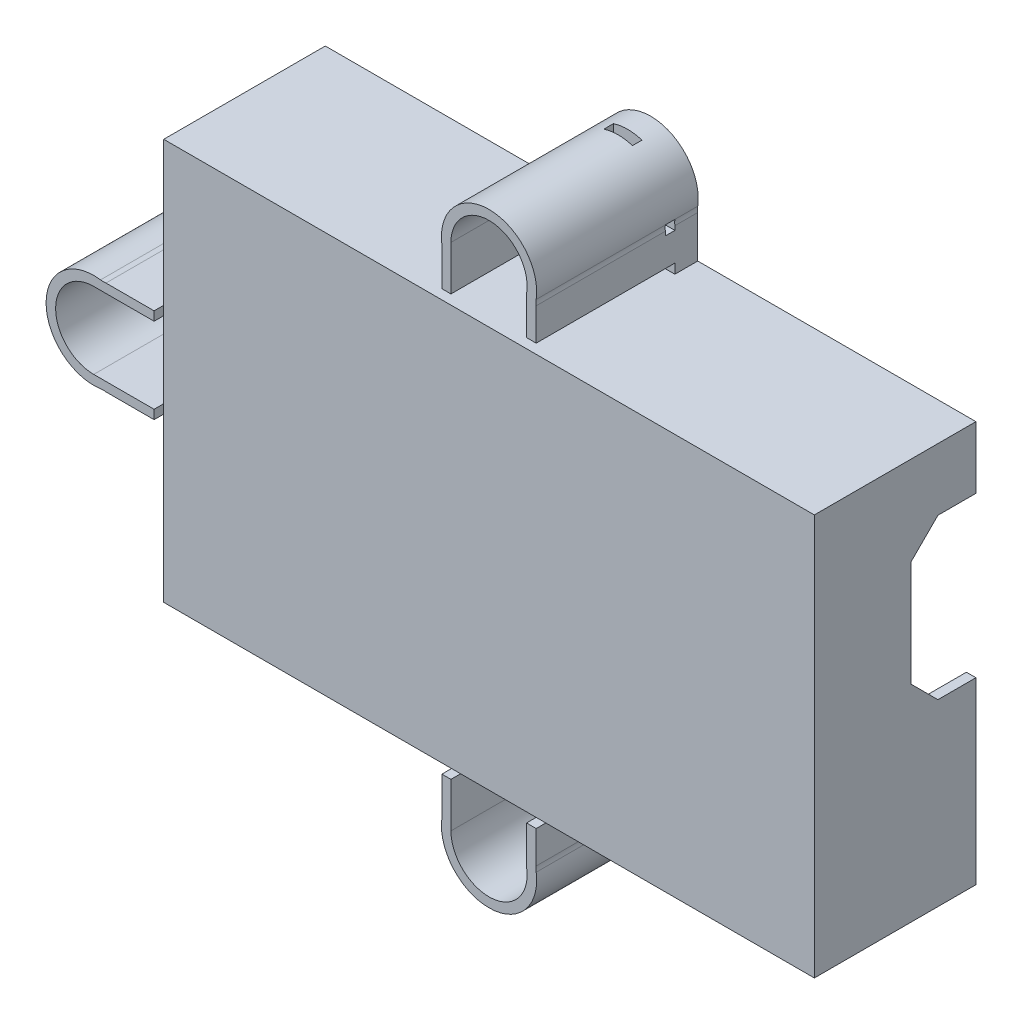
SolidWorks part; units mm, degrees
ref_plane "Front Plane" through (0, 0, 0) normal (0, 0, 1) x (1, 0, 0)
ref_plane "Top Plane" through (0, 0, 0) normal (0, 1, 0) x (1, 0, 0)
ref_plane "Right Plane" through (0, 0, 0) normal (1, 0, 0) x (0, 0, -1)
sketch "Sketch1" plane through (0, 0, 0) normal (0, 0, 1) x (1, 0, 0)
  line L0 (-16.375, 9.825) -> (16.375, -9.825) construction
  line L1 (-16.375, -9.825) -> (-16.575, -9.825) construction
  line L2 (16.575, 10.025) -> (-16.575, 10.025)
  line L3 (16.575, 10.025) -> (16.575, -10.025)
  line L4 (-16.375, 9.825) -> (-16.375, -9.825)
  line L5 (-16.375, -9.825) -> (16.375, -9.825)
  line L6 (16.375, -9.825) -> (16.375, 9.825)
  line L7 (16.375, 9.825) -> (-16.375, 9.825)
  line L8 (-16.375, 9.825) -> (-16.375, -9.825)
  line L9 (-16.375, -9.825) -> (16.375, -9.825)
  line L10 (16.375, -9.825) -> (16.375, 9.825)
  line L11 (16.375, 9.825) -> (-16.375, 9.825)
  line L12 (16.575, -10.025) -> (-16.575, -10.025)
  line L13 (-16.575, 10.025) -> (-16.575, -10.025)
  line L14 (16.575, 10.025) -> (-16.575, -10.025) construction
  line L15 (-13.9701, -11.875) -> (-3.4641, -11.875)
  line L18 (3.4641, -11.875) -> (13.9701, -11.875)
  line L19 (14.8161, -12.3418) -> (24.6724, -27.981)
  line L20 (31.4404, -23.7156) -> (19.404, -4.6171)
  line L21 (19.25, -4.084) -> (19.25, 4.084)
  line L22 (19.404, 4.6171) -> (31.4404, 23.7156)
  line L23 (24.6724, 27.981) -> (14.8161, 12.3418)
  line L24 (13.9701, 11.875) -> (3.4641, 11.875)
  line L25 (-3.4641, 11.875) -> (-13.9701, 11.875)
  line L26 (-14.8161, 12.3418) -> (-24.6724, 27.981)
  line L27 (-31.4404, 23.7156) -> (-19.404, 4.6171)
  line L28 (-19.25, 4.084) -> (-19.25, 3.4641)
  line L29 (-19.25, -3.4641) -> (-19.25, -4.084)
  line L30 (-19.404, -4.6171) -> (-31.4404, -23.7156)
  line L31 (-24.6724, -27.981) -> (-14.8161, -12.3418)
  line L32 (-13.9701, -11.875) -> (-3.4641, -11.875)
  line L33 (3.4641, -11.875) -> (13.9701, -11.875)
  line L34 (14.8161, -12.3418) -> (24.6724, -27.981)
  line L35 (31.4404, -23.7156) -> (19.404, -4.6171)
  line L36 (19.25, -4.084) -> (19.25, 4.084)
  line L37 (19.404, 4.6171) -> (31.4404, 23.7156)
  line L38 (24.6724, 27.981) -> (14.8161, 12.3418)
  line L39 (13.9701, 11.875) -> (3.4641, 11.875)
  line L40 (-3.4641, 11.875) -> (-13.9701, 11.875)
  line L41 (-14.8161, 12.3418) -> (-24.6724, 27.981)
  line L42 (-31.4404, 23.7156) -> (-19.404, 4.6171)
  line L43 (-19.25, 4.084) -> (-19.25, 3.4641)
  line L44 (-19.25, -3.4641) -> (-19.25, -4.084)
  line L45 (-19.404, -4.6171) -> (-31.4404, -23.7156)
  line L46 (-24.6724, -27.981) -> (-14.8161, -12.3418)
  line L47 (16.575, -10.025) -> (-16.575, 10.025) construction
  line L48 (-16.375, -9.825) -> (-16.375, -10.025) construction
  line L49 (-16.575, -10.025) -> (-17.075, -10.025) construction
  line L50 (17.075, 10.525) -> (-17.075, 10.525)
  line L51 (17.075, 10.525) -> (17.075, -10.525)
  line L52 (17.075, -10.525) -> (-17.075, -10.525)
  line L53 (-17.075, 10.525) -> (-17.075, -10.525)
  line L54 (17.075, 10.525) -> (-17.075, -10.525) construction
  line L55 (17.075, -10.525) -> (-17.075, 10.525) construction
  line L56 (-16.575, -10.025) -> (-16.575, -10.525) construction
  line L57 (-20.3929, -2.4744) -> (-17.075, -2.4744)
  line L58 (-20.3929, 2.4744) -> (-17.075, 2.4744)
  line L59 (-2.4744, -13.0179) -> (-2.4744, -10.525)
  line L60 (2.4744, -13.0179) -> (2.4744, -10.525)
  line L61 (-2.4744, 13.0179) -> (-2.4744, 10.525)
  line L62 (2.4744, 13.0179) -> (2.4744, 10.525)
  circle A0 centre (0, -13.375) radius 1.25
  circle A1 centre (-20.75, 0) radius 1.25
  circle A2 centre (0, 13.375) radius 1.25
  arc A32 (-2.4744, -13.0179) -> (-3.4641, -11.875) centre (-3.4641, -12.875) ccw
  arc A33 (-2.4744, -13.0179) -> (2.4744, -13.0179) centre (0, -13.375) ccw
  arc A34 (3.4641, -11.875) -> (2.4744, -13.0179) centre (3.4641, -12.875) ccw
  arc A35 (14.8161, -12.3418) -> (13.9701, -11.875) centre (13.9701, -12.875) ccw
  arc A36 (24.7505, -28.8963) -> (24.6724, -27.981) centre (23.8264, -28.5142) ccw
  arc A37 (24.7505, -28.8963) -> (32.2325, -24.1809) centre (31.8198, -31.8198) ccw
  arc A38 (31.4404, -23.7156) -> (32.2325, -24.1809) centre (32.2864, -23.1824) ccw
  arc A39 (19.25, -4.084) -> (19.404, -4.6171) centre (20.25, -4.084) ccw
  arc A40 (19.404, 4.6171) -> (19.25, 4.084) centre (20.25, 4.084) ccw
  arc A41 (32.2325, 24.1809) -> (31.4404, 23.7156) centre (32.2864, 23.1824) ccw
  arc A42 (32.2325, 24.1809) -> (24.7505, 28.8963) centre (31.8198, 31.8198) ccw
  arc A43 (24.6724, 27.981) -> (24.7505, 28.8963) centre (23.8264, 28.5142) ccw
  arc A44 (13.9701, 11.875) -> (14.8161, 12.3418) centre (13.9701, 12.875) ccw
  arc A45 (2.4744, 13.0179) -> (3.4641, 11.875) centre (3.4641, 12.875) ccw
  arc A46 (2.4744, 13.0179) -> (-2.4744, 13.0179) centre (0, 13.375) ccw
  arc A47 (-3.4641, 11.875) -> (-2.4744, 13.0179) centre (-3.4641, 12.875) ccw
  arc A48 (-14.8161, 12.3418) -> (-13.9701, 11.875) centre (-13.9701, 12.875) ccw
  arc A49 (-24.7505, 28.8963) -> (-24.6724, 27.981) centre (-23.8264, 28.5142) ccw
  arc A50 (-24.7505, 28.8963) -> (-32.2325, 24.1809) centre (-31.8198, 31.8198) ccw
  arc A51 (-31.4404, 23.7156) -> (-32.2325, 24.1809) centre (-32.2864, 23.1824) ccw
  arc A52 (-19.25, 4.084) -> (-19.404, 4.6171) centre (-20.25, 4.084) ccw
  arc A53 (-20.3929, 2.4744) -> (-19.25, 3.4641) centre (-20.25, 3.4641) ccw
  arc A54 (-20.3929, 2.4744) -> (-20.3929, -2.4744) centre (-20.75, 0) ccw
  arc A55 (-19.25, -3.4641) -> (-20.3929, -2.4744) centre (-20.25, -3.4641) ccw
  arc A56 (-19.404, -4.6171) -> (-19.25, -4.084) centre (-20.25, -4.084) ccw
  arc A57 (-32.2325, -24.1809) -> (-31.4404, -23.7156) centre (-32.2864, -23.1824) ccw
  arc A58 (-32.2325, -24.1809) -> (-24.7505, -28.8963) centre (-31.8198, -31.8198) ccw
  arc A59 (-24.6724, -27.981) -> (-24.7505, -28.8963) centre (-23.8264, -28.5142) ccw
  arc A60 (-13.9701, -11.875) -> (-14.8161, -12.3418) centre (-13.9701, -12.875) ccw
  arc A61 (-2.4744, -13.0179) -> (-3.4641, -11.875) centre (-3.4641, -12.875) ccw
  arc A62 (-2.4744, -13.0179) -> (2.4744, -13.0179) centre (0, -13.375) ccw
  arc A63 (3.4641, -11.875) -> (2.4744, -13.0179) centre (3.4641, -12.875) ccw
  arc A64 (14.8161, -12.3418) -> (13.9701, -11.875) centre (13.9701, -12.875) ccw
  arc A65 (24.7505, -28.8963) -> (24.6724, -27.981) centre (23.8264, -28.5142) ccw
  arc A66 (24.7505, -28.8963) -> (32.2325, -24.1809) centre (31.8198, -31.8198) ccw
  arc A67 (31.4404, -23.7156) -> (32.2325, -24.1809) centre (32.2864, -23.1824) ccw
  arc A68 (19.25, -4.084) -> (19.404, -4.6171) centre (20.25, -4.084) ccw
  arc A69 (19.404, 4.6171) -> (19.25, 4.084) centre (20.25, 4.084) ccw
  arc A70 (32.2325, 24.1809) -> (31.4404, 23.7156) centre (32.2864, 23.1824) ccw
  arc A71 (32.2325, 24.1809) -> (24.7505, 28.8963) centre (31.8198, 31.8198) ccw
  arc A72 (24.6724, 27.981) -> (24.7505, 28.8963) centre (23.8264, 28.5142) ccw
  arc A73 (13.9701, 11.875) -> (14.8161, 12.3418) centre (13.9701, 12.875) ccw
  arc A74 (2.4744, 13.0179) -> (3.4641, 11.875) centre (3.4641, 12.875) ccw
  arc A75 (2.4744, 13.0179) -> (-2.4744, 13.0179) centre (0, 13.375) ccw
  arc A76 (-3.4641, 11.875) -> (-2.4744, 13.0179) centre (-3.4641, 12.875) ccw
  arc A77 (-14.8161, 12.3418) -> (-13.9701, 11.875) centre (-13.9701, 12.875) ccw
  arc A78 (-24.7505, 28.8963) -> (-24.6724, 27.981) centre (-23.8264, 28.5142) ccw
  arc A79 (-24.7505, 28.8963) -> (-32.2325, 24.1809) centre (-31.8198, 31.8198) ccw
  arc A80 (-31.4404, 23.7156) -> (-32.2325, 24.1809) centre (-32.2864, 23.1824) ccw
  arc A81 (-19.25, 4.084) -> (-19.404, 4.6171) centre (-20.25, 4.084) ccw
  arc A82 (-20.3929, 2.4744) -> (-19.25, 3.4641) centre (-20.25, 3.4641) ccw
  arc A83 (-20.3929, 2.4744) -> (-20.3929, -2.4744) centre (-20.75, 0) ccw
  arc A84 (-19.25, -3.4641) -> (-20.3929, -2.4744) centre (-20.25, -3.4641) ccw
  arc A85 (-19.404, -4.6171) -> (-19.25, -4.084) centre (-20.25, -4.084) ccw
  arc A86 (-32.2325, -24.1809) -> (-31.4404, -23.7156) centre (-32.2864, -23.1824) ccw
  arc A87 (-32.2325, -24.1809) -> (-24.7505, -28.8963) centre (-31.8198, -31.8198) ccw
  arc A88 (-24.6724, -27.981) -> (-24.7505, -28.8963) centre (-23.8264, -28.5142) ccw
  arc A89 (-13.9701, -11.875) -> (-14.8161, -12.3418) centre (-13.9701, -12.875) ccw
  point P6 (0, 0)
  point P25 (0, 0)
  dimension "D4" = 0.5
  dimension "D5" = 2.5
  dimension "D1" = 0
  dimension "D2" = 0
  dimension "D3" = 0.2
extrude "Boss-Extrude1" add sketch "Sketch1" along normal offset from surface (7.98 mm away) 2.5 contours A84 L57 L53 L58 A82 A83 | L50 L53 L52 L51 L13 L2 L3 L12 | A63 L60 L52 L59 A61 A62 | A76 L61 L50 L62 A74 A75 region at (-2.4011, -11.6286, 0) region at (-9.7747, -10.1238, 0) region at (-18.5911, -2.3949, 0) region at (0, 10.5982, 0) offset beyond the face yes
sketch "Sketch2" plane through (0, 0, 7.98) normal (0, 0, 1) x (1, 0, 0)
  line L0 (-2.5, 10.525) -> (2.4744, 10.525)
  line L1 (-17.075, 2.5) -> (-17.075, -2.5)
  line L2 (-2.5, -10.525) -> (2.4744, -10.525)
  line L6 (-20.1071, -2.4744) -> (-17.075, -2.4744)
  line L7 (-20.1071, -2.4744) -> (-17.075, -2.4744)
  line L8 (-17.075, -2.4744) -> (-17.075, -10.525)
  line L9 (-17.075, -2.4744) -> (-17.075, -10.525)
  line L20 (-17.075, -10.525) -> (-2.4744, -10.525)
  line L21 (-17.075, -10.525) -> (-2.4744, -10.525)
  line L22 (-2.4744, -10.525) -> (-2.4744, -12.7321)
  line L23 (-2.4744, -10.525) -> (-2.4744, -12.7321)
  line L24 (2.4744, -12.7321) -> (2.4744, -10.525)
  line L25 (2.4744, -12.7321) -> (2.4744, -10.525)
  line L26 (2.4744, -10.525) -> (17.075, -10.525)
  line L27 (2.4744, -10.525) -> (17.075, -10.525)
  line L28 (17.075, -10.525) -> (17.075, 10.525)
  line L29 (17.075, -10.525) -> (17.075, 10.525)
  line L30 (17.075, 10.525) -> (2.4744, 10.525)
  line L31 (17.075, 10.525) -> (2.4744, 10.525)
  line L32 (2.4744, 10.525) -> (2.4744, 12.7321)
  line L33 (2.4744, 10.525) -> (2.4744, 12.7321)
  line L34 (-2.4744, 12.7321) -> (-2.4744, 10.525)
  line L35 (-2.4744, 12.7321) -> (-2.4744, 10.525)
  line L36 (-2.4744, 10.525) -> (-17.075, 10.525)
  line L37 (-2.4744, 10.525) -> (-17.075, 10.525)
  line L38 (-17.075, 10.525) -> (-17.075, 2.4744)
  line L39 (-17.075, 10.525) -> (-17.075, 2.4744)
  line L40 (-17.075, 2.4744) -> (-20.1071, 2.4744)
  line L41 (-17.075, 2.4744) -> (-20.1071, 2.4744)
  arc A9 (-20.1071, -2.4744) -> (-20.3929, -2.4744) centre (-20.25, -3.4641) ccw
  arc A10 (-20.1071, -2.4744) -> (-20.3929, -2.4744) centre (-20.25, -3.4641) ccw
  arc A11 (-2.4744, -13.0179) -> (-2.4744, -12.7321) centre (-3.4641, -12.875) ccw
  arc A12 (-2.4744, -13.0179) -> (-2.4744, -12.7321) centre (-3.4641, -12.875) ccw
  arc A13 (-2.4744, -13.0179) -> (2.4744, -13.0179) centre (0, -13.375) ccw
  arc A14 (-2.4744, -13.0179) -> (2.4744, -13.0179) centre (0, -13.375) ccw
  arc A15 (2.4744, -12.7321) -> (2.4744, -13.0179) centre (3.4641, -12.875) ccw
  arc A16 (2.4744, -12.7321) -> (2.4744, -13.0179) centre (3.4641, -12.875) ccw
  arc A17 (2.4744, 13.0179) -> (2.4744, 12.7321) centre (3.4641, 12.875) ccw
  arc A18 (2.4744, 13.0179) -> (2.4744, 12.7321) centre (3.4641, 12.875) ccw
  arc A19 (2.4744, 13.0179) -> (-2.4744, 13.0179) centre (0, 13.375) ccw
  arc A20 (2.4744, 13.0179) -> (-2.4744, 13.0179) centre (0, 13.375) ccw
  arc A21 (-2.4744, 12.7321) -> (-2.4744, 13.0179) centre (-3.4641, 12.875) ccw
  arc A22 (-2.4744, 12.7321) -> (-2.4744, 13.0179) centre (-3.4641, 12.875) ccw
  arc A23 (-20.3929, 2.4744) -> (-20.1071, 2.4744) centre (-20.25, 3.4641) ccw
  arc A24 (-20.3929, 2.4744) -> (-20.1071, 2.4744) centre (-20.25, 3.4641) ccw
  arc A25 (-20.3929, 2.4744) -> (-20.3929, -2.4744) centre (-20.75, 0) ccw
  arc A26 (-20.3929, 2.4744) -> (-20.3929, -2.4744) centre (-20.75, 0) ccw
  dimension "D1" = 0
extrude "Cut-Extrude1" cut sketch "Sketch2" against normal offset from surface (6.78 mm away) 1.2 contours L0 | L1 | L2 region at (0, 12.9704, 7.98) region at (-19.9289, 0, 7.98) region at (0, -12.9704, 7.98) up to face at (-5.364, 0, 0)
sketch "Sketch3" plane through (17.075, 0, 0) normal (1, 0, 0) x (0, 0, -1)
  line L0 (0, 10.525) -> (0, -10.525) construction
  line L1 (0, 7.265) -> (-3.395, 7.265)
  line L2 (0, 7.265) -> (0, -1.115)
  line L3 (0, -1.115) -> (-3.395, -1.115)
  line L4 (-3.395, 7.265) -> (-3.395, -1.115)
  line L6 (-1.3, 7.065) -> (-1.3, 7.265) construction
  line L7 (-1.3, -0.915) -> (-1.3, -1.115) construction
  line L8 (-3.195, 5.375) -> (-3.395, 5.375) construction
  dimension "D1" = 0.2
extrude "Cut-Extrude2" cut sketch "Sketch3" against normal up to next
chamfer "Chamfer1" distance 1.4 angle 45 2 edges at (16.825, -1.115, 3.395) (16.825, 7.265, 3.395)
sketch "Sketch4" plane through (0, 0, 7.98) normal (0, 0, 1) x (1, 0, 0)
  line L4 (-17.075, 10.525) -> (-17.075, -10.525)
  line L8 (-17.075, 10.525) -> (-17.075, -10.525)
  line L17 (-17.075, -10.525) -> (17.075, -10.525)
  line L18 (-17.075, -10.525) -> (17.075, -10.525)
  line L25 (17.075, -10.525) -> (17.075, 10.525)
  line L26 (17.075, -10.525) -> (17.075, 10.525)
  line L27 (17.075, 10.525) -> (-17.075, 10.525)
  line L28 (17.075, 10.525) -> (-17.075, 10.525)
  dimension "D1" = 0
extrude "Boss-Extrude2" add sketch "Sketch4" along normal blind 0.5
sketch "Sketch8" plane through (-17.075, 0, 0) normal (-1, 0, 0) x (0, 0, 1)
  line L1 (5.93, 3.385) -> (7.98, 3.385)
  line L2 (5.93, 3.385) -> (5.93, -3.385)
  line L3 (5.93, -3.385) -> (7.98, -3.385)
  line L4 (7.98, 3.385) -> (7.98, -3.385)
  line L7 (7.08, 3.385) -> (5.93, 3.385) construction
  line L8 (5.93, -3.385) -> (7.08, -3.385) construction
  line L9 (5.93, 3.385) -> (5.93, 2.4) construction
  line L10 (7.98, -3.985) -> (7.98, -2.4) construction
extrude "Cut-Extrude3" cut sketch "Sketch8" against normal up to next
sketch "Sketch9" plane through (0, 0, 7.98) normal (0, 0, -1) x (-1, 0, 0)
  line L1 (16.575, 2.4) -> (17.075, 2.4)
  line L2 (16.575, 2.4) -> (16.575, 3.385)
  line L3 (16.575, 3.385) -> (17.075, 3.385)
  line L4 (17.075, 2.4) -> (17.075, 3.385)
  line L5 (16.575, -2.4) -> (17.075, -2.4)
  line L6 (16.575, -2.4) -> (16.575, -3.385)
  line L7 (16.575, -3.385) -> (17.075, -3.385)
  line L8 (17.075, -2.4) -> (17.075, -3.385)
extrude "Boss-Extrude6" add sketch "Sketch9" along normal blind 0.8
sketch "Sketch5" plane through (0, 0, 1.2) normal (0, 0, 1) x (1, 0, 0)
  line L0 (-2, -13.375) -> (-2, -11.0315)
  line L1 (-17.075, 0) -> (17.075, 0) construction
  line L2 (17.075, -10.525) -> (17.075, 10.525) construction
  line L3 (-2.4744, 11.0315) -> (2.4744, 11.0315)
  line L4 (-2, 13.375) -> (-2, 11.0315)
  line L5 (1.9679, 13.0179) -> (1.9679, 11.0315)
  line L6 (-17.5815, 2.4744) -> (-17.5815, -2.4744)
  line L7 (-17.075, 0) -> (-17.5815, 0) construction
  line L8 (-20.75, 2) -> (-17.5815, 2)
  line L9 (-2.4744, 12.7321) -> (-2.4744, 10.525) construction
  line L10 (-2.4744, 10.525) -> (2.4744, 10.525) construction
  line L11 (2.4744, 10.525) -> (2.4744, 12.7321) construction
  line L12 (-20.1071, -2.4744) -> (-17.075, -2.4744) construction
  line L13 (-17.075, -2.4744) -> (-17.075, 2.4744) construction
  line L14 (-17.075, 2.4744) -> (-20.1071, 2.4744) construction
  line L15 (2.4744, -12.7321) -> (2.4744, -10.525) construction
  line L16 (2.4744, -10.525) -> (-2.4744, -10.525) construction
  line L17 (-2.4744, -10.525) -> (-2.4744, -12.7321) construction
  line L18 (-2.4744, 12.7321) -> (-2.4744, 10.525)
  line L19 (-2.4744, 10.525) -> (2.4744, 10.525)
  line L20 (2.4744, 10.525) -> (2.4744, 12.7321)
  line L21 (-20.1071, -2.4744) -> (-17.075, -2.4744)
  line L22 (-20.75, -2) -> (-17.5815, -2)
  line L23 (-17.075, -2.4744) -> (-17.075, 2.4744)
  line L24 (-17.075, 2.4744) -> (-20.1071, 2.4744)
  line L25 (2.4744, -12.7321) -> (2.4744, -10.525)
  line L26 (2.4744, -10.525) -> (-2.4744, -10.525)
  line L27 (-2.4744, -10.525) -> (-2.4744, -12.7321)
  line L28 (-2.4744, -11.0315) -> (2.4744, -11.0315)
  line L29 (0, -11.0315) -> (0, -10.525) construction
  line L30 (2.4744, -13.0179) -> (1.9679, -13.0179) construction
  line L31 (1.9679, -13.0179) -> (1.9679, -11.0315)
  circle A0 centre (0, 13.375) radius 2
  circle A1 centre (-20.75, 0) radius 2
  arc A3 (2.4744, 13.0179) -> (2.4744, 12.7321) centre (3.4641, 12.875) ccw construction
  arc A4 (2.4744, 13.0179) -> (-2.4744, 13.0179) centre (0, 13.375) ccw construction
  arc A5 (-2.4744, 12.7321) -> (-2.4744, 13.0179) centre (-3.4641, 12.875) ccw construction
  arc A6 (-20.3929, 2.4744) -> (-20.1071, 2.4744) centre (-20.25, 3.4641) ccw construction
  arc A7 (-20.3929, 2.4744) -> (-20.3929, -2.4744) centre (-20.75, 0) ccw construction
  arc A8 (-20.1071, -2.4744) -> (-20.3929, -2.4744) centre (-20.25, -3.4641) ccw construction
  arc A9 (-2.4744, -13.0179) -> (-2.4744, -12.7321) centre (-3.4641, -12.875) ccw construction
  arc A10 (-2.4744, -13.0179) -> (2.4744, -13.0179) centre (0, -13.375) ccw construction
  arc A11 (2.4744, -12.7321) -> (2.4744, -13.0179) centre (3.4641, -12.875) ccw construction
  arc A12 (2.4744, 13.0179) -> (2.4744, 12.7321) centre (3.4641, 12.875) ccw
  arc A13 (2.4744, 13.0179) -> (-2.4744, 13.0179) centre (0, 13.375) ccw
  arc A14 (-2.4744, 12.7321) -> (-2.4744, 13.0179) centre (-3.4641, 12.875) ccw
  arc A15 (-20.3929, 2.4744) -> (-20.1071, 2.4744) centre (-20.25, 3.4641) ccw
  arc A16 (-20.3929, 2.4744) -> (-20.3929, -2.4744) centre (-20.75, 0) ccw
  arc A17 (-20.1071, -2.4744) -> (-20.3929, -2.4744) centre (-20.25, -3.4641) ccw
  arc A18 (-2.4744, -13.0179) -> (-2.4744, -12.7321) centre (-3.4641, -12.875) ccw
  arc A19 (-2.4744, -13.0179) -> (2.4744, -13.0179) centre (0, -13.375) ccw
  arc A20 (2.4744, -12.7321) -> (2.4744, -13.0179) centre (3.4641, -12.875) ccw
  circle A21 centre (0, -13.375) radius 2
  line M51 (-20.1071, -2.4744) -> (-17.075, -2.4744)
  line M52 (-17.075, 2.4744) -> (-20.1071, 2.4744)
  arc M53 (-20.1071, 2.4744) -> (-20.3929, 2.4744) centre (-20.25, 3.4641) cw
  arc M54 (-20.3929, 2.4744) -> (-20.3929, -2.4744) centre (-20.75, 0) ccw
  arc M55 (-20.3929, -2.4744) -> (-20.1071, -2.4744) centre (-20.25, -3.4641) cw
  dimension "D1" = 0.5
extrude "Boss-Extrude3" add sketch "Sketch5" along normal up to surface (7.28 mm away) contours A14 L18 L3 L4 A0 L5 L20 A12 A13 | A1 L8 L6 L22 M52 M53 M54 M55 M51 | A21 L0 L28 L27 A18 A19 A20 L25 L31 region at (0, -15.4446, 1.2) region at (-2.4047, 11.8818, 1.2) region at (-17.6571, 2.2372, 1.2) up to face at (0, 0, 8.48)
sketch "Sketch11" plane through (0, 0, 7.98) normal (0, 0, -1) x (-1, 0, 0)
  line L24 (16.675, -4.085) -> (16.675, -2.3)
  line L25 (16.675, -2.3) -> (15.385, -2.3)
  line L26 (15.385, -2.3) -> (15.385, 2.3)
  line L27 (15.385, 2.3) -> (16.675, 2.3)
  line L28 (16.675, 2.3) -> (16.675, 4.085)
  line L29 (16.675, 4.085) -> (10.255, 4.085)
  line L30 (10.255, 4.085) -> (10.255, 2.4)
  line L31 (10.255, 2.4) -> (5.655, 2.4)
  line L32 (5.655, 2.4) -> (5.655, -2.4)
  line L33 (5.655, -2.4) -> (10.255, -2.4)
  line L34 (10.255, -2.4) -> (10.255, -4.085)
  line L35 (10.255, -4.085) -> (16.675, -4.085)
  line L36 (16.675, -4.085) -> (16.675, -2.3)
  line L37 (16.675, -2.3) -> (15.385, -2.3)
  line L38 (15.385, -2.3) -> (15.385, 2.3)
  line L39 (15.385, 2.3) -> (16.675, 2.3)
  line L40 (16.675, 2.3) -> (16.675, 4.085)
  line L41 (16.675, 4.085) -> (10.255, 4.085)
  line L42 (10.255, 4.085) -> (10.255, 2.4)
  line L43 (10.255, 2.4) -> (5.655, 2.4)
  line L44 (5.655, 2.4) -> (5.655, -2.4)
  line L45 (5.655, -2.4) -> (10.255, -2.4)
  line L46 (10.255, -2.4) -> (10.255, -4.085)
  line L47 (10.255, -4.085) -> (16.675, -4.085)
  line L48 (5.655, 1.9) -> (3.655, 1.9)
  line L49 (3.655, 0) -> (17.385, 0) construction
  line L50 (5.655, -1.9) -> (3.655, -1.9)
  line L51 (16.575, 6.085) -> (16.575, 4.085)
  line L53 (16.575, 10.025) -> (16.575, 2.4) construction
  line L54 (16.575, -6.085) -> (16.575, -4.085)
  line L55 (16.575, -2.4) -> (16.575, -10.025) construction
  line L60 (18.675, -6.085) -> (18.675, -0.3)
  line L61 (18.675, -0.3) -> (17.385, -0.3)
  line L62 (17.385, -0.3) -> (17.385, 0.3)
  line L63 (17.385, 0.3) -> (18.675, 0.3)
  line L64 (18.675, 0.3) -> (18.675, 6.085)
  line L65 (18.675, 6.085) -> (8.255, 6.085)
  line L66 (8.255, 6.085) -> (8.255, 4.4)
  line L67 (8.255, 4.4) -> (3.655, 4.4)
  line L68 (3.655, 4.4) -> (3.655, -4.4)
  line L69 (3.655, -4.4) -> (8.255, -4.4)
  line L70 (8.255, -4.4) -> (8.255, -6.085)
  line L71 (8.255, -6.085) -> (18.675, -6.085)
  line L72 (18.675, -6.085) -> (18.675, -0.3)
  line L73 (18.675, -0.3) -> (17.385, -0.3)
  line L74 (17.385, -0.3) -> (17.385, 0.3)
  line L75 (17.385, 0.3) -> (18.675, 0.3)
  line L76 (18.675, 0.3) -> (18.675, 6.085)
  line L77 (18.675, 6.085) -> (8.255, 6.085)
  line L78 (8.255, 6.085) -> (8.255, 4.4)
  line L79 (8.255, 4.4) -> (3.655, 4.4)
  line L80 (3.655, 4.4) -> (3.655, -4.4)
  line L81 (3.655, -4.4) -> (8.255, -4.4)
  line L82 (8.255, -4.4) -> (8.255, -6.085)
  line L83 (8.255, -6.085) -> (18.675, -6.085)
  line M27 (16.575, -10.025) -> (16.575, -2.4)
  line M31 (16.575, 2.4) -> (16.575, 10.025)
  dimension "D3" = 0.5
  dimension "D1" = 0.1
  dimension "D2" = 2.1
extrude "Boss-Extrude7" add sketch "Sketch11" along normal blind 2.5 contours L79 L80 L48 L44 L43 L42 L41 L77 L78 M31 | L82 L83 L47 L46 L45 L44 L50 L80 L81 M27 region at (-9.8383, -4.2692, 7.98) region at (-9.8383, 4.2692, 7.98)
sketch "Sketch12" plane through (0, 0, 7.98) normal (0, 0, -1) x (-1, 0, 0)
  line L0 (16.575, -6.085) -> (16.575, -10.025) construction
  line L1 (-3.0335, 0) -> (1.6631, 0) construction
  line L2 (16.575, 8.055) -> (14.605, 8.055)
  line L3 (16.575, 8.055) -> (16.575, 6.085)
  line L4 (16.575, 6.085) -> (14.605, 6.085)
  line L5 (16.575, -8.055) -> (14.605, -8.055)
  line L6 (16.575, -8.055) -> (16.575, -6.085)
  line L7 (16.575, -6.085) -> (14.605, -6.085)
  line L8 (14.605, -8.055) -> (14.605, -6.085)
  line L9 (8.255, -6.085) -> (16.575, -6.085) construction
  line L10 (14.605, 8.055) -> (14.605, 6.085)
  line L11 (-16.575, 10.025) -> (-16.575, -10.025) construction
  line L12 (-14.605, 2) -> (-16.575, 2)
  line L13 (-14.605, 2) -> (-14.605, -2)
  line L14 (-14.605, -2) -> (-16.575, -2)
  line L15 (-16.575, 2) -> (-16.575, -2)
  line L16 (-14.605, 2) -> (-16.575, -2) construction
  line L17 (-14.605, -2) -> (-16.575, 2) construction
  point P16 (-15.59, 0)
  dimension "D1" = 4
extrude "Boss-Extrude8" add sketch "Sketch12" along normal up to surface (3.95 mm away)
sketch "Sketch13" plane through (-17.075, 0, 0) normal (-1, 0, 0) x (0, 0, 1)
  line L0 (7.18, 2.4) -> (7.18, 3.385) construction
  line L1 (7.98, 2.4) -> (7.18, 2.4)
  line L2 (7.98, 2.4) -> (7.98, 2.9)
  line L3 (7.98, 2.9) -> (7.18, 2.9)
  line L4 (7.18, 2.4) -> (7.18, 2.9)
  line L5 (5.93, 0) -> (7.98, 0) construction
  line L6 (7.18, 3.385) -> (5.43, 3.385)
  line L7 (7.18, 3.385) -> (7.18, 3.885)
  line L8 (7.18, 3.885) -> (5.43, 3.885)
  line L9 (5.43, 3.385) -> (5.43, 3.885)
  line L10 (5.93, 3.385) -> (5.93, -3.385) construction
  line L11 (7.98, -2) -> (7.98, 2) construction
  line L12 (5.43, 1.6925) -> (5.93, 1.6925) construction
  line L13 (5.43, 3.385) -> (5.93, 3.385)
  line L14 (5.43, 3.385) -> (5.43, -3.385)
  line L15 (5.93, 0) -> (5.93, -3.385)
  line L16 (5.93, 3.385) -> (5.93, 0)
  line L17 (7.98, -2.4) -> (7.98, -2.9)
  line L18 (7.98, -2.9) -> (7.18, -2.9)
  line L19 (7.18, -3.385) -> (7.18, -3.885)
  line L20 (7.18, -3.885) -> (5.43, -3.885)
  line L21 (5.43, -3.385) -> (5.43, -3.885)
  line L22 (5.43, 3.385) -> (5.43, -3.385)
  line L23 (1.2, -2.4744) -> (1.2, 2.4744) construction
  line L24 (0, 2.5) -> (1.2, 2.5)
  line L25 (0, 2.5) -> (0, 5)
  line L26 (0, 5) -> (1.2, 5)
  line L27 (1.2, 2.5) -> (1.2, 5)
  line M12 (7.98, -2.4) -> (7.18, -2.4)
  line M13 (7.18, -2.4) -> (7.18, -3.385)
  line M14 (7.18, -3.385) -> (5.93, -3.385)
  line M15 (5.93, -3.385) -> (5.93, 3.385)
  line M16 (5.93, 3.385) -> (7.18, 3.385)
  line M17 (7.18, 3.385) -> (7.18, 2.4)
  line M18 (7.18, 2.4) -> (7.98, 2.4)
  line M22 (0, 10.525) -> (0, 2.4744)
  dimension "D1" = 0.5
  dimension "D2" = 2.5
extrude "Cut-Extrude4" cut sketch "Sketch13" against normal up to next contours L9 L6 L7 L8 M16 | L2 L3 M17 M18 | L14 L21 L20 L19 L6 M14 M15 | L18 L17 M12 M13 | L24 L27 L26 M22 region at (-17.075, -2.65, 7.58) region at (-17.075, 3.635, 6.305) region at (-17.075, 2.65, 7.58) region at (-17.075, -0.7466, 5.8084) region at (-17.075, 3.75, 0.6)
sketch "Sketch14" plane through (0, 0, 5.48) normal (0, 0, -1) x (-1, 0, 0)
  line L0 (16.575, 4.085) -> (10.255, 4.085) construction
  line L1 (16.575, 6.085) -> (14.175, 6.085)
  line L2 (16.575, 6.085) -> (16.575, 3.685)
  line L3 (16.575, 3.685) -> (14.175, 3.685)
  line L4 (14.175, 6.085) -> (14.175, 3.685)
  line L5 (3.655, 1.9) -> (3.655, -1.9) construction
  line L6 (3.655, 0) -> (16.575, 0) construction
  line L8 (16.575, -6.085) -> (16.575, -3.685)
  line L9 (16.575, -6.085) -> (14.175, -6.085)
  line L10 (14.175, -6.085) -> (14.175, -3.685)
  line L11 (16.575, -3.685) -> (14.175, -3.685)
  line L12 (5.655, 2.4) -> (5.655, 1.9) construction
  line L13 (3.655, 4.4) -> (5.655, 4.4)
  line L14 (3.655, 4.4) -> (3.655, 1.5)
  line L15 (3.655, 1.5) -> (5.655, 1.5)
  line L16 (5.655, 4.4) -> (5.655, 1.5)
  line L17 (15.375, 3.685) -> (15.375, 4.085) construction
  line L18 (16.575, 4.085) -> (10.255, 4.085) construction
  line L19 (4.655, 1.5) -> (4.655, 1.9) construction
  line L20 (5.655, 1.9) -> (3.655, 1.9) construction
  line L21 (3.655, -4.4) -> (5.655, -4.4)
  line L22 (5.655, -4.4) -> (5.655, -1.5)
  line L23 (3.655, -1.5) -> (5.655, -1.5)
  line L24 (3.655, -4.4) -> (3.655, -1.5)
  line L25 (16.575, 2.5) -> (16.575, -10.025) construction
  dimension "D1" = 0.4
extrude "Boss-Extrude9" add sketch "Sketch14" along normal blind 0.6
ref_plane "Plane1" through (0, 0, 2.95) normal (0, 0, -1) x (-1, 0, 0)
sketch "Sketch16" plane through (0, 0, 2.95) normal (0, 0, -1) x (-1, 0, 0)
  line L0 (-16.575, 10.025) -> (16.575, 10.025) construction
  line L1 (6.075, 10.025) -> (8.575, 10.025)
  line L2 (6.075, 10.025) -> (6.075, 9.325)
  line L3 (6.075, 9.325) -> (8.575, 9.325)
  line L4 (8.575, 10.025) -> (8.575, 9.325)
  line L6 (16.575, 10.025) -> (16.575, 5) construction
  line L8 (-16.575, 10.025) -> (-14.075, 10.025)
  line L9 (-16.575, 10.025) -> (-16.575, 9.325)
  line L10 (-16.575, 9.325) -> (-14.075, 9.325)
  line L11 (-14.075, 10.025) -> (-14.075, 9.325)
  line L12 (16.575, -10.025) -> (14.075, -10.025)
  line L13 (16.575, -10.025) -> (16.575, -9.325)
  line L14 (16.575, -9.325) -> (14.075, -9.325)
  line L15 (14.075, -10.025) -> (14.075, -9.325)
  line L16 (-16.575, -10.025) -> (-14.075, -10.025)
  line L17 (-16.575, -10.025) -> (-16.575, -9.325)
  line L18 (-16.575, -9.325) -> (-14.075, -9.325)
  line L19 (-14.075, -10.025) -> (-14.075, -9.325)
  dimension "D1" = 2.5
  dimension "D2" = 0.7
  dimension "D3" = 8
extrude "Boss-Extrude13" add sketch "Sketch16" along normal blind 0.8
chamfer "Chamfer2" distance 1 angle 45 2 edges at (-10.255, 3.2425, 5.48) (-10.255, -3.2425, 5.48)
sketch "Sketch15" plane through (0, 0, 1.2) normal (0, 0, 1) x (1, 0, 0)
  line L0 (0, 15.375) -> (0, 15.875) construction
  line L1 (2.4744, 11.0315) -> (2.4744, 12.7321) construction
  line L2 (-0.75, 16.021) -> (0.75, 16.021)
  line L3 (-0.75, 16.021) -> (-0.75, 15.229)
  line L4 (-0.75, 15.229) -> (0.75, 15.229)
  line L5 (0.75, 16.021) -> (0.75, 15.229)
  line L6 (-0.75, 16.021) -> (0.75, 15.229) construction
  line L7 (-0.75, 15.229) -> (0.75, 16.021) construction
  line L8 (-2.4744, 13.0179) -> (2.4744, 13.0179)
  line L9 (-2.4744, 13.0179) -> (-2.4744, 12.5179)
  line L10 (-2.4744, 12.5179) -> (2.4744, 12.5179)
  line L11 (2.4744, 13.0179) -> (2.4744, 12.5179)
  line L12 (-17.075, 0) -> (17.075, 0) construction
  line L13 (-17.075, 10.525) -> (-17.075, -10.525) construction
  line L14 (17.075, -10.525) -> (17.075, 10.525) construction
  line L15 (0.75, -16.021) -> (0.75, -15.229)
  line L16 (-0.75, -16.021) -> (0.75, -16.021)
  line L17 (-0.75, -16.021) -> (-0.75, -15.229)
  line L18 (-0.75, -15.229) -> (0.75, -15.229)
  line L19 (2.4744, -13.0179) -> (2.4744, -12.5179)
  line L20 (-2.4744, -13.0179) -> (2.4744, -13.0179)
  line L21 (-2.4744, -13.0179) -> (-2.4744, -12.5179)
  line L22 (-2.4744, -12.5179) -> (2.4744, -12.5179)
  line L23 (-23.25, 0) -> (-22.604, 0) construction
  line L25 (-23.25, -0.75) -> (-22.604, -0.75)
  line L26 (-23.25, -0.75) -> (-23.25, 0.75)
  line L27 (-23.25, 0.75) -> (-22.604, 0.75)
  line L28 (-22.604, -0.75) -> (-22.604, 0.75)
  line L29 (-23.25, -0.75) -> (-22.604, 0.75) construction
  line L30 (-23.25, 0.75) -> (-22.604, -0.75) construction
  line L31 (-20.75, 2.5) -> (-20.25, 2.5)
  line L32 (-20.75, 2.5) -> (-20.75, -2.4744)
  line L33 (-20.75, -2.4744) -> (-20.25, -2.4744)
  line L34 (-20.25, 2.5) -> (-20.25, -2.4744)
  line L35 (-20.75, 2.5) -> (-20.75, -2.5) construction
  arc A0 (1.9679, 13.0179) -> (-2, 13.375) centre (0, 13.375) ccw construction
  arc A1 (1.9679, 13.0179) -> (-2, 13.375) centre (0, 13.375) ccw construction
  arc A2 (2.4744, 13.0179) -> (-2.4744, 13.0179) centre (0, 13.375) ccw construction
  arc A5 (-20.75, 2) -> (-20.75, -2) centre (-20.75, 0) ccw construction
  arc A6 (-20.3929, 2.4744) -> (-20.3929, -2.4744) centre (-20.75, 0) ccw construction
  point P11 (0, 15.625)
  point P44 (-22.927, 0)
  dimension "D1" = 1.5
  dimension "D2" = 0.5
extrude "Cut-Extrude5" cut sketch "Sketch15" along normal blind 0.5
